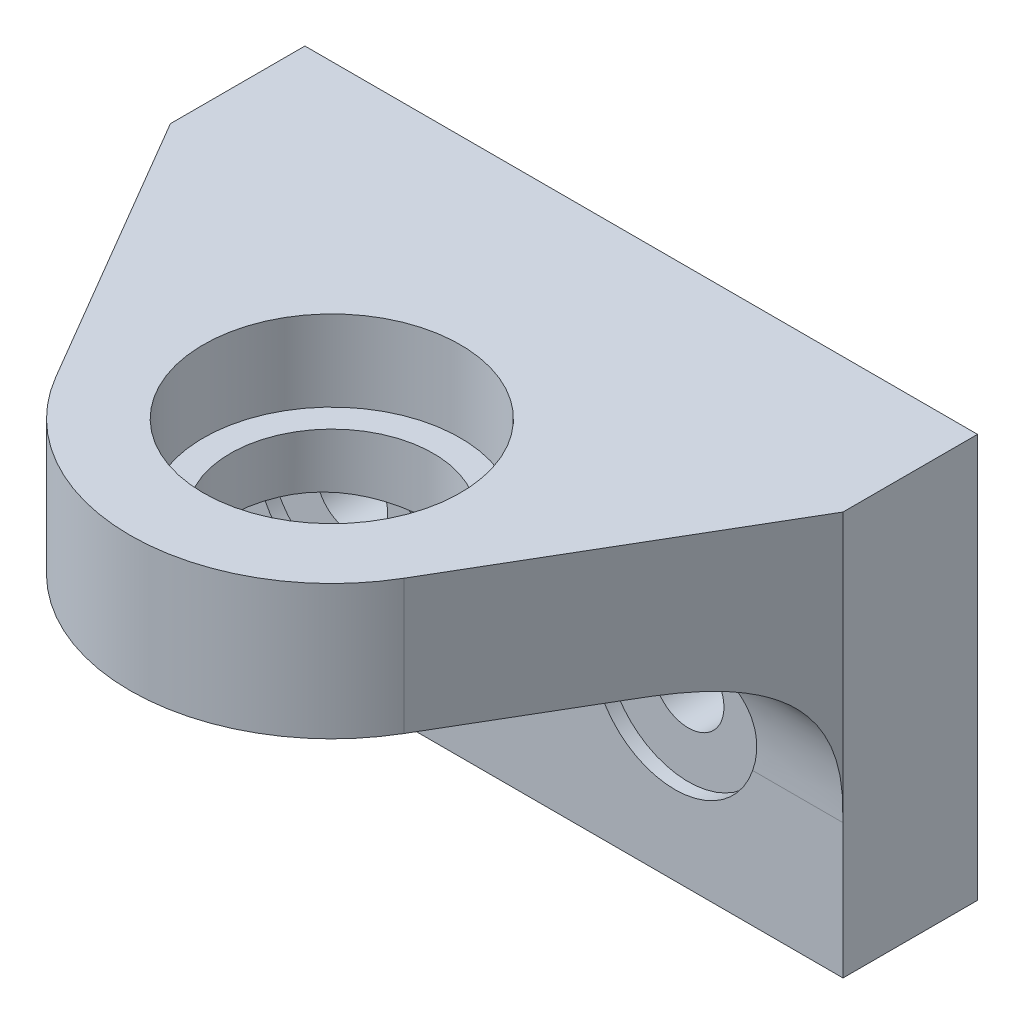
SolidWorks part; units mm, degrees
material "PET"
ref_plane "Front Plane" through (0, 0, 0) normal (0, 0, 1) x (1, 0, 0)
ref_plane "Top Plane" through (0, 0, 0) normal (0, 1, 0) x (1, 0, 0)
ref_plane "Right Plane" through (0, 0, 0) normal (1, 0, 0) x (0, 0, -1)
sketch "Sketch1" plane through (0, 0, 0) normal (0, 0, 1) x (1, 0, 0)
  line L1 (-25, 15) -> (25, 15)
  line L2 (-25, 15) -> (-25, -15)
  line L3 (-25, -15) -> (25, -15)
  line L4 (25, 15) -> (25, -15)
  line L5 (-25, 15) -> (25, -15) construction
  line L6 (-25, -15) -> (25, 15) construction
  point P0 (0, 0)
  dimension "D1" = 50
  dimension "D2" = 30
extrude "Boss-Extrude1" add sketch "Sketch1" along normal blind 10
sketch "Sketch8" plane through (0, 15, 0) normal (0, 1, 0) x (1, 0, 0)
  line L0 (-25, -10) -> (-12.9427, -30.582)
  line L5 (12.9427, -30.582) -> (25, -10)
  line L6 (25, -10) -> (-25, -10)
  line L7 (0, -10) -> (0, -38) construction
  line L8 (25, 0) -> (-25, 0) construction
  arc A0 (-12.9427, -30.582) -> (12.9427, -30.582) centre (0, -23) ccw
  dimension "D2" = 30
  dimension "D1" = 23
extrude "Boss-Extrude3" add sketch "Sketch8" against normal blind 10
sketch "Sketch14" plane through (0, 0, 10) normal (0, 0, 1) x (1, 0, 0)
  line L0 (-25, -3) -> (-12.5, -3) construction
  line L2 (-12.5, -3) -> (12.5, -3) construction
  line L3 (12.5, -3) -> (25, -3) construction
  line L5 (-25, 5) -> (-25, -15) construction
  line L6 (25, -15) -> (25, 5) construction
  point P2 (-12.5, -3)
  point P6 (12.5, -3)
  point P18 (-12.5, -3)
  point P20 (12.5, -3)
  dimension "D1" = 25
  dimension "D2" = 12
hole_wizard "CBORE for M5 Hex Head Bolt1" positions "Sketch14" profile "Sketch10" counterbore size "M5" standard "ANSI Metric" end condition through all
sketch "Sketch10" plane through (12.5, -3, 10) normal (1, 0, 0) x (0, -1, 0)
  line L0 (0, 0) -> (0, 10)
  line L1 (0, 10) -> (2.65, 10)
  line L3 (2.65, 10) -> (2.65, 1)
  line L4 (2.65, 1) -> (6.12, 1)
  line L5 (6.12, 1) -> (6.12, 0)
  line L7 (6.12, 0) -> (0, 0)
  line L11 (0, -6.35) -> (0, 107.95) construction
  dimension "Thru Hole Dia." = 5.3
  dimension "Thru Hole Depth" = 10
  dimension "C'Bore Dia." = 12.24
  dimension "C'Bore Depth" = 1
fillet "Fillet1" radius 10 1 edges at (0, 5, 10) curvature continuous yes
sketch "Sketch15" plane through (0, 15, 0) normal (0, 1, 0) x (1, 0, 0)
  circle A0 centre (0, -23) radius 9.55
  arc A3 (-12.9427, -30.582) -> (12.9427, -30.582) centre (0, -23) ccw construction
  dimension "D1" = 19.1
extrude "Cut-Extrude1" cut sketch "Sketch15" against normal blind 6
sketch "Sketch16" plane through (0, 9, 0) normal (0, 1, 0) x (1, 0, 0)
  circle A0 centre (0, -23) radius 7.55
  circle A1 centre (0, -23) radius 9.55 construction
  dimension "D1" = 2
extrude "Cut-Extrude2" cut sketch "Sketch16" against normal through all
